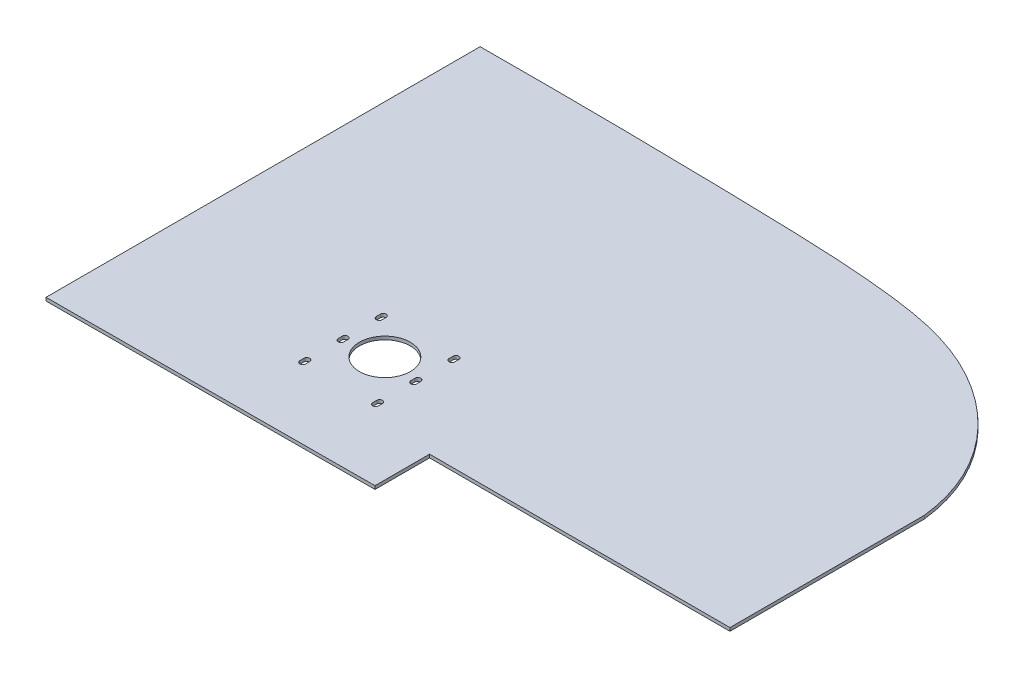
SolidWorks part; units mm, degrees
ref_plane "Alzado" through (0, 0, 0) normal (0, 0, 1) x (1, 0, 0)
ref_plane "Planta" through (0, 0, 0) normal (0, 1, 0) x (1, 0, 0)
ref_plane "Vista lateral" through (0, 0, 0) normal (1, 0, 0) x (0, 0, -1)
sketch "Croquis1" plane through (0, 0, 0) normal (0, 1, 0) x (1, 0, 0)
  line L0 (-872.7705, -164.3587) -> (-420.2125, -164.3587) construction
  line L1 (-420.2125, -164.3587) -> (-420.2125, 152.6413) construction
  line L2 (-599.3125, -124.3587) -> (-545.2125, -124.3587) construction
  line L3 (-599.3125, -124.3587) -> (-599.3125, -47.6587) construction
  line L4 (-599.3125, -47.6587) -> (-545.2125, -47.6587) construction
  line L5 (-545.2125, -124.3587) -> (-545.2125, -47.6587) construction
  line L6 (-872.7705, -164.3587) -> (-872.7705, 15.6413) construction
  line L7 (-193.9987, 152.6413) -> (-193.9987, -164.3587) construction
  line L8 (484.7732, -164.3587) -> (484.7732, 15.6413) construction
  line L9 (157.2152, -124.3587) -> (157.2152, -47.6587) construction
  line L10 (211.3152, -47.6587) -> (157.2152, -47.6587) construction
  line L11 (211.3152, -124.3587) -> (211.3152, -47.6587) construction
  line L12 (211.3152, -124.3587) -> (157.2152, -124.3587) construction
  line L13 (32.2152, -164.3587) -> (32.2152, 152.6413) construction
  line L14 (484.7732, -164.3587) -> (32.2152, -164.3587) construction
  circle A0 centre (-607.8125, -61.6587) radius 2 construction
  circle A1 centre (-537.8125, -61.6587) radius 2 construction
  circle A2 centre (-537.8125, -75.6587) radius 2 construction
  circle A3 centre (-537.8125, -89.6587) radius 2 construction
  circle A4 centre (-537.8125, -103.6587) radius 2 construction
  circle A5 centre (-537.8125, -117.6587) radius 2 construction
  circle A6 centre (-607.8125, -75.6587) radius 2 construction
  circle A7 centre (-607.8125, -89.6587) radius 2 construction
  circle A8 centre (-607.8125, -103.6587) radius 2 construction
  circle A9 centre (-607.8125, -117.6587) radius 2 construction
  circle A10 centre (219.8152, -117.6587) radius 2 construction
  circle A11 centre (219.8152, -103.6587) radius 2 construction
  circle A12 centre (219.8152, -89.6587) radius 2 construction
  circle A13 centre (219.8152, -75.6587) radius 2 construction
  circle A14 centre (149.8152, -117.6587) radius 2 construction
  circle A15 centre (149.8152, -103.6587) radius 2 construction
  circle A16 centre (149.8152, -89.6587) radius 2 construction
  circle A17 centre (149.8152, -75.6587) radius 2 construction
  circle A18 centre (149.8152, -61.6587) radius 2 construction
  circle A19 centre (219.8152, -61.6587) radius 2 construction
  spline S0 degree 3 poles (-872.7705, 15.6413) (-870.1587, 51.1179) (-859.9034, 77.3702) (-827.0825, 109.5392) (-802.8418, 124.9112) (-759.5593, 140.6884) (-735.913, 143.2787) (-720.4915, 144.8169) knots 0 0 0 0 0.358065 0.430061 0.687747 0.747962 1 1 1 1 construction
  spline S1 degree 3 poles (-420.2125, 152.6413) (-520.4329, 151.1718) (-620.5344, 152.5539) (-720.4915, 144.8169) knots 0 0 0 0 1 1 1 1 construction
  spline S2 degree 3 poles (32.2152, 152.6413) (132.4356, 151.1718) (232.5371, 152.5539) (332.4942, 144.8169) knots 0 0 0 0 1 1 1 1 construction
  spline S3 degree 3 poles (484.7732, 15.6413) (482.1614, 51.1179) (471.9061, 77.3702) (439.0852, 109.5392) (414.8445, 124.9112) (371.5619, 140.6884) (347.9157, 143.2787) (332.4942, 144.8169) knots 0 0 0 0 0.358065 0.430061 0.687747 0.747962 1 1 1 1 construction
  point P4 (-646.4915, -164.3587)
  point P67 (258.4942, -164.3587)
  dimension "D6" = 4
  dimension "D1" = 180
  dimension "D2" = 76.7
  dimension "D3" = 54.1
  dimension "D4" = 125
  dimension "D5" = 40
  dimension "D7" = 8.5
  dimension "D8" = 14
  dimension "D9" = 317
sketch "Croquis3" plane through (0, 0, 0) normal (0, 1, 0) x (1, 0, 0)
  line L0 (492.3059, -125.2441) -> (272.3059, -125.2441)
  line L1 (272.3059, -125.2441) -> (272.3059, -165.2441)
  line L2 (167.5459, -57.4188) -> (167.5459, -54.4188) construction
  line L3 (272.3059, -165.2441) -> (32.3059, -166.2441)
  line L4 (492.3059, -125.2441) -> (492.3059, 17.1595)
  line L5 (32.3059, -166.2441) -> (32.3059, 151.7559)
  line L6 (165.4459, -57.4188) -> (165.4459, -54.4188)
  line L7 (169.6459, -57.4188) -> (169.6459, -54.4188)
  line L8 (222.9659, -57.4188) -> (222.9659, -54.4188)
  line L9 (218.7659, -57.4188) -> (218.7659, -54.4188)
  line L10 (220.8659, -57.4188) -> (220.8659, -54.4188) construction
  line L11 (222.9659, -85.4188) -> (222.9659, -82.4188)
  line L12 (218.7659, -85.4188) -> (218.7659, -82.4188)
  line L13 (220.8659, -85.4188) -> (220.8659, -82.4188) construction
  line L14 (222.9659, -113.4188) -> (222.9659, -110.4188)
  line L15 (218.7659, -113.4188) -> (218.7659, -110.4188)
  line L16 (220.8659, -113.4188) -> (220.8659, -110.4188) construction
  line L17 (169.6459, -85.4188) -> (169.6459, -82.4188)
  line L18 (165.4459, -85.4188) -> (165.4459, -82.4188)
  line L19 (167.5459, -85.4188) -> (167.5459, -82.4188) construction
  line L20 (169.6459, -113.4188) -> (169.6459, -110.4188)
  line L21 (165.4459, -113.4188) -> (165.4459, -110.4188)
  line L22 (167.5459, -113.4188) -> (167.5459, -110.4188) construction
  circle A0 centre (194.2059, -79.9188) radius 18.65
  arc A1 (165.4459, -57.4188) -> (169.6459, -57.4188) centre (167.5459, -57.4188) ccw
  arc A2 (169.6459, -54.4188) -> (165.4459, -54.4188) centre (167.5459, -54.4188) ccw
  arc A3 (218.7659, -57.4188) -> (222.9659, -57.4188) centre (220.8659, -57.4188) ccw
  arc A4 (222.9659, -54.4188) -> (218.7659, -54.4188) centre (220.8659, -54.4188) ccw
  arc A5 (218.7659, -85.4188) -> (222.9659, -85.4188) centre (220.8659, -85.4188) ccw
  arc A6 (222.9659, -82.4188) -> (218.7659, -82.4188) centre (220.8659, -82.4188) ccw
  arc A7 (218.7659, -113.4188) -> (222.9659, -113.4188) centre (220.8659, -113.4188) ccw
  arc A8 (222.9659, -110.4188) -> (218.7659, -110.4188) centre (220.8659, -110.4188) ccw
  arc A9 (165.4459, -85.4188) -> (169.6459, -85.4188) centre (167.5459, -85.4188) ccw
  arc A10 (169.6459, -82.4188) -> (165.4459, -82.4188) centre (167.5459, -82.4188) ccw
  arc A11 (165.4459, -113.4188) -> (169.6459, -113.4188) centre (167.5459, -113.4188) ccw
  arc A12 (169.6459, -110.4188) -> (165.4459, -110.4188) centre (167.5459, -110.4188) ccw
  spline S1 degree 3 poles (32.3059, 151.7559) (102.587, 152.083) (202.5087, 151.1682) (322.8677, 147.214) (426.0281, 131.8038) (486.0219, 73.5154) (492.3059, 17.1595) knots 0 0 0 0 0.403913 0.577103 0.694611 1 1 1 1
  point P0 (392.585, 125.1991)
  point P12 (167.5459, -55.9188)
  point P29 (220.8659, -55.9188)
  point P36 (220.8659, -83.9188)
  point P43 (220.8659, -111.9188)
  point P50 (167.5459, -83.9188)
  point P57 (167.5459, -111.9188)
  dimension "D1" = 37.3
  dimension "D7" = 2.1
  dimension "D2" = 318
  dimension "D3" = 220
  dimension "D4" = 40
  dimension "D5" = 161.9
  dimension "D6" = 85.65
  dimension "D8" = 3
  dimension "D9" = 26.66
  dimension "D10" = 24
  dimension "D11" = 2
  dimension "D12" = 3
extrude "Saliente-Extruir1" add sketch "Croquis3" along normal blind 2.4
